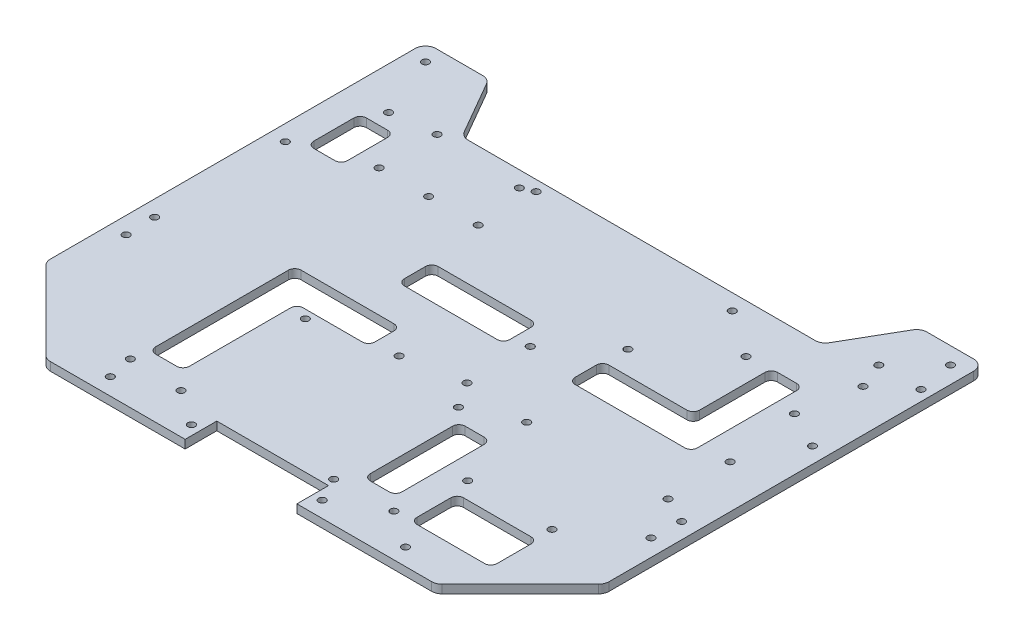
SolidWorks part; units mm, degrees
material "Acier non allié"
ref_plane "Front" through (0, 0, 0) normal (0, 0, 1) x (1, 0, 0)
ref_plane "Top" through (0, 0, 0) normal (0, 1, 0) x (1, 0, 0)
ref_plane "Right" through (0, 0, 0) normal (1, 0, 0) x (0, 0, -1)
sketch "Main scetch" plane through (0, 0, 0) normal (0, 1, 0) x (1, 0, 0)
  line L1 (0, 0) -> (132.5, 0) construction
  line L2 (0, 0) -> (0, 220) construction
  line L3 (0, 220) -> (132.5, 220) construction
  line L4 (132.5, 0) -> (132.5, 220) construction
  line L13 (-92.5, 0) -> (92.5, 0)
  line L14 (92.5, 0) -> (132.5, 40)
  line L15 (132.5, 40) -> (132.5, 220)
  line L16 (132.5, 220) -> (102.5, 220)
  line L17 (102.5, 220) -> (85.1795, 190)
  line L18 (85.1795, 190) -> (-85.1795, 190)
  line L19 (-102.5, 220) -> (-85.1795, 190)
  line L20 (-132.5, 220) -> (-102.5, 220)
  line L21 (-132.5, 40) -> (-132.5, 220)
  line L22 (-92.5, 0) -> (-132.5, 40)
  point P11 (0, 190)
  dimension "132.5" = 132.5
  dimension "D2" = 220
  dimension "D1" = 40
  dimension "D3" = 40
  dimension "D4" = 30
  dimension "D5" = 60
  dimension "D6" = 30
extrude "Main extrusion" add sketch "Main scetch" along normal blind 4
fillet "Congé1" radius 5 10 edges at (-132.5, 2, -40) (-92.5, 2, 0) (92.5, 2, 0) (132.5, 2, -40) (132.5, 2, -220) (102.5, 2, -220) (85.1795, 2, -190) (-85.1795, 2, -190) (-102.5, 2, -220) (-132.5, 2, -220)
sketch "Esquisse1" plane through (0, 4, 0) normal (0, 1, 0) x (1, 0, 0)
  line L0 (0, 0) -> (0, 218.5516) construction
  line L1 (132.5, 42.0711) -> (132.5, 215) construction
  line L2 (127.5, 220) -> (105.3868, 220) construction
  line L3 (-90.4289, 0) -> (90.4289, 0) construction
  circle A0 centre (70, 8) radius 1
  circle A1 centre (124.5, 70) radius 1
  circle A2 centre (124.5, 212) radius 1
  circle A3 centre (-124.5, 212) radius 1
  circle A4 centre (-124.5, 70) radius 1
  circle A5 centre (-70, 8) radius 1
  dimension "D1" = 2
  dimension "D2" = 2
  dimension "D3" = 2
  dimension "D4" = 8
  dimension "D5" = 8
  dimension "D6" = 8
  dimension "D7" = 8
  dimension "D8" = 70
  dimension "D9" = 70
extrude "Enlèv. mat.-Extru.1" cut sketch "Esquisse1" against normal through all
hole_wizard "Dégagement M31" positions "Esquisse2" profile "Esquisse3" hole size "M3" standard "ISO" end condition through all
sketch "Esquisse2" plane through (0, 4, 0) normal (0, 1, 0) x (1, 0, 0)
  point P0 (-124.5, 212)
  point P3 (-124.5, 70)
  point P6 (-70, 8)
  point P9 (70, 8)
  point P12 (124.5, 70)
  point P15 (124.5, 212)
sketch "Esquisse3" plane through (-124.5, 4, -212) normal (1, 0, 0) x (0, 0, 1)
  line L0 (0, 0) -> (0, 4)
  line L1 (0, 4) -> (1.7, 4)
  line L2 (1.7, 4) -> (1.7, 0)
  line L5 (1.7, 0) -> (0, 0)
  line L11 (0, -6.35) -> (0, 107.95) construction
  dimension "Diamètre du perçage jusqu'au prochain" = 3.4
  dimension "Profondeur du perçage jusqu'au prochain" = 4
sketch "Esquisse4" plane through (0, 4, 0) normal (0, 1, 0) x (1, 0, 0)
  line L0 (-132.5, 215) -> (-132.5, 42.0711) construction
  line L1 (-125, 146) -> (-125, 84) construction
  line L2 (82.2927, 190) -> (-82.2927, 190) construction
  line L3 (132.5, 42.0711) -> (132.5, 215) construction
  line L4 (-90.4289, 0) -> (90.4289, 0) construction
  line L5 (127.5, 220) -> (105.3868, 220) construction
  line L8 (-105.3868, 220) -> (-127.5, 220) construction
  line L9 (-31, 7.5) -> (31, 7.5) construction
  line L10 (125, 146) -> (125, 84) construction
  line L11 (-26.5, 0) -> (26.5, 0)
  line L12 (-26.5, 0) -> (-26.5, 15)
  line L13 (-26.5, 15) -> (26.5, 15)
  line L14 (26.5, 0) -> (26.5, 15)
  line L15 (50.5, 182.5) -> (112.5, 182.5) construction
  line L16 (-112.5, 182.5) -> (-50.5, 182.5) construction
  circle A1 centre (-68.5, 185) radius 1 construction
  circle A5 centre (72.5, 167) radius 1
  circle A6 centre (41.5, 142) radius 1
  circle A7 centre (107.5, 155) radius 1
  circle A8 centre (127.5, 195) radius 1
  circle A9 centre (112, 120) radius 1
  circle A10 centre (112.5, 90) radius 1
  circle A11 centre (17.2, 120) radius 1
  circle A12 centre (17.2, 90) radius 1
  circle A13 centre (47.5, 88) radius 1
  circle A14 centre (57.5, 50) radius 1
  circle A15 centre (97.5, 50) radius 1
  circle A16 centre (52.5, 20) radius 1
  circle A17 centre (-10, 85) radius 1
  circle A18 centre (-72.5, 20) radius 1
  circle A19 centre (107.5, 195) radius 1
  circle A23 centre (-47.5, 78) radius 1
  circle A24 centre (25.14, 78) radius 1
  circle A25 centre (-47.5, 19.07) radius 1
  circle A26 centre (25.1096, 18.82) radius 1
  circle A31 centre (-125, 146) radius 1
  circle A32 centre (-125, 84) radius 1
  circle A33 centre (-31, 7.5) radius 1
  circle A34 centre (31, 7.5) radius 1
  circle A35 centre (125, 146) radius 1
  circle A36 centre (125, 84) radius 1
  circle A37 centre (50.5, 182.5) radius 1
  circle A38 centre (112.5, 182.5) radius 1
  circle A39 centre (-112.5, 182.5) radius 1
  circle A40 centre (-50.5, 182.5) radius 1
  circle A41 centre (-45, 185) radius 1
  circle A42 centre (-45, 157.5) radius 1
  circle A43 centre (-68.5, 157.5) radius 1
  circle A44 centre (-92, 157.5) radius 1
  circle A45 centre (-92, 185) radius 1
  point P54 (0, 0)
  point P63 (-125, 115)
  point P69 (0, 7.5)
  point P74 (0, 15)
  point P79 (125, 115)
  dimension "D4" = 2
  dimension "D13" = 2
  dimension "D16" = 2
  dimension "D19" = 2
  dimension "D24" = 2
  dimension "D25" = 2
  dimension "D28" = 2
  dimension "D30" = 2
  dimension "D32" = 2
  dimension "D36" = 2
  dimension "D37" = 2
  dimension "D40" = 2
  dimension "D48" = 2
  dimension "D49" = 2
  dimension "D50" = 2
  dimension "D52" = 2
  dimension "D11" = 2
  dimension "D12" = 2
  dimension "D65" = 2
  dimension "D66" = 2
  dimension "D72" = 2
  dimension "D73" = 2
  dimension "D77" = 2
  dimension "D78" = 2
  dimension "D85" = 2
  dimension "D86" = 2
  dimension "D89" = 2
  dimension "D90" = 2
  dimension "D94" = 2
  dimension "D95" = 2
  dimension "D58" = 2
  dimension "D59" = 2
  dimension "D62" = 2
  dimension "D63" = 2
  dimension "D69" = 2
  dimension "D14" = 205
  dimension "D15" = 23
  dimension "D20" = 25
  dimension "D21" = 65
  dimension "D22" = 5
  dimension "D23" = 25
  dimension "D26" = 20.5
  dimension "D27" = 100
  dimension "D29" = 30
  dimension "D31" = 115.3
  dimension "D33" = 115.3
  dimension "D34" = 132
  dimension "D35" = 85
  dimension "D38" = 50
  dimension "D39" = 75
  dimension "D41" = 35
  dimension "D42" = 80
  dimension "D43" = 20
  dimension "D44" = 20
  dimension "D45" = 205
  dimension "D46" = 85
  dimension "D47" = 142.5
  dimension "D51" = 25
  dimension "D53" = 25
  dimension "D54" = 5
  dimension "D55" = 64
  dimension "D7" = 59.18
  dimension "D8" = 72.64
  dimension "D9" = 58.93
  dimension "D10" = 72.61
  dimension "D67" = 85
  dimension "D68" = 78
  dimension "D17" = 25
  dimension "D18" = 31
  dimension "D76" = 62
  dimension "D74" = 7.5
  dimension "D75" = 105
  dimension "D79" = 7.5
  dimension "D80" = 132.5
  dimension "D81" = 62
  dimension "D82" = 15
  dimension "D83" = 53
  dimension "D84" = 62
  dimension "D87" = 7.5
  dimension "D88" = 105
  dimension "D91" = 62
  dimension "D92" = 7.5
  dimension "D96" = 62
  dimension "D97" = 7.5
  dimension "D98" = 20
  dimension "D93" = 20
  dimension "D56" = 87.5
  dimension "D57" = 5
  dimension "D60" = 27.5
  dimension "D61" = 23.5
  dimension "D64" = 23.5
  dimension "D70" = 27.5
extrude "Enlèv. mat.-Extru.2" cut sketch "Esquisse4" against normal through all
hole_wizard "Dégagement M32" positions "Esquisse5" profile "Esquisse6" hole size "M3" standard "ISO" end condition through all
sketch "Esquisse5" plane through (0, 4, 0) normal (0, 1, 0) x (1, 0, 0)
  point P9 (17.2, 120)
  point P18 (41.5, 142)
  point P21 (72.5, 167)
  point P24 (107.5, 155)
  point P27 (127.5, 195)
  point P30 (112, 120)
  point P33 (112.5, 90)
  point P36 (47.5, 88)
  point P39 (17.2, 90)
  point P42 (57.5, 50)
  point P45 (97.5, 50)
  point P48 (-10, 85)
  point P51 (-72.5, 20)
  point P54 (52.5, 20)
  point P57 (107.5, 195)
  point P86 (-47.5, 78)
  point P89 (25.14, 78)
  point P92 (-47.5, 19.07)
  point P95 (25.1096, 18.82)
  point P114 (-125, 146)
  point P117 (-125, 84)
  point P121 (-31, 7.5)
  point P124 (31, 7.5)
  point P128 (125, 146)
  point P131 (125, 84)
  point P134 (-112.5, 182.5)
  point P137 (-50.5, 182.5)
  point P140 (50.5, 182.5)
  point P143 (112.5, 182.5)
  point P146 (-92, 185)
  point P149 (-92, 157.5)
  point P152 (-68.5, 157.5)
  point P155 (-45, 157.5)
  point P158 (-45, 185)
sketch "Esquisse6" plane through (17.2, 4, -120) normal (1, 0, 0) x (0, 0, 1)
  line L0 (0, 0) -> (0, 4)
  line L1 (0, 4) -> (1.7, 4)
  line L2 (1.7, 4) -> (1.7, 0)
  line L5 (1.7, 0) -> (0, 0)
  line L11 (0, -6.35) -> (0, 107.95) construction
  dimension "Diamètre du perçage jusqu'au prochain" = 3.4
  dimension "Profondeur du perçage jusqu'au prochain" = 4
sketch "Esquisse7" plane through (0, 4, 0) normal (0, 1, 0) x (1, 0, 0)
  line L0 (-90.4289, 0) -> (-26.5, 0) construction
  line L1 (-40.5, 131) -> (9.5, 131)
  line L2 (-40.5, 131) -> (-40.5, 115)
  line L3 (-40.5, 115) -> (9.5, 115)
  line L4 (9.5, 131) -> (9.5, 115)
  line L5 (-132.5, 215) -> (-132.5, 42.0711) construction
  line L8 (40.5, 115) -> (98.5, 115)
  line L10 (132.5, 42.0711) -> (132.5, 215) construction
  line L11 (40.5, 115) -> (40.5, 131)
  line L12 (83.5, 168) -> (98.5, 168)
  line L13 (83.5, 168) -> (83.5, 131)
  line L15 (98.5, 168) -> (98.5, 115)
  line L16 (40.5, 131) -> (83.5, 131)
  line L17 (-105.3868, 220) -> (-127.5, 220) construction
  line L18 (60.5, 42) -> (98.5, 42)
  line L19 (60.5, 42) -> (60.5, 20)
  line L20 (60.5, 20) -> (98.5, 20)
  line L21 (98.5, 42) -> (98.5, 20)
  line L22 (-118.5, 175) -> (-102.5, 175)
  line L23 (-118.5, 175) -> (-118.5, 150)
  line L24 (-118.5, 150) -> (-102.5, 150)
  line L25 (-102.5, 175) -> (-102.5, 150)
  line L27 (-71.5, 28) -> (-55.5, 28)
  line L28 (-71.5, 28) -> (-71.5, 83)
  line L30 (-55.5, 28) -> (-55.5, 82)
  line L31 (31.5, 71.82) -> (46.5, 71.82)
  line L32 (31.5, 71.82) -> (31.5, 26.82)
  line L33 (31.5, 26.82) -> (46.5, 26.82)
  line L34 (46.5, 71.82) -> (46.5, 26.82)
  line L35 (-71.5, 97) -> (-21.5, 97)
  line L36 (-71.5, 97) -> (-71.5, 83)
  line L37 (-55.5, 82) -> (-21.5, 82)
  line L38 (-21.5, 97) -> (-21.5, 82)
  circle A0 centre (-72.5, 20) radius 1.7 construction
  circle A1 centre (-47.5, 78) radius 1.7 construction
  circle A2 centre (25.1096, 18.82) radius 1.7 construction
  circle A3 centre (52.5, 20) radius 1.7 construction
  dimension "D19" = 8
  dimension "D20" = 8
  dimension "D24" = 15
  dimension "D1" = 50
  dimension "D2" = 16
  dimension "D3" = 131
  dimension "D4" = 92
  dimension "D5" = 16
  dimension "D6" = 53
  dimension "D7" = 43
  dimension "D8" = 115
  dimension "D9" = 72
  dimension "D10" = 38
  dimension "D11" = 34
  dimension "D12" = 15
  dimension "D13" = 22
  dimension "D14" = 20
  dimension "D15" = 30
  dimension "D16" = 70
  dimension "D17" = 16
  dimension "D18" = 25
  dimension "D21" = 16
  dimension "D22" = 55
  dimension "D23" = 8
  dimension "6" = 6
  dimension "D25" = 45
  dimension "D26" = 50
  dimension "D27" = 54
  dimension "D28" = 15
extrude "Enlèv. mat.-Extru.3" cut sketch "Esquisse7" against normal up to surface (4 mm away) up to face at (17.2, 0, -118.3)
fillet "Congé2" radius 3 28 edges at (60.5, 2, -42) (60.5, 2, -20) (98.5, 2, -20) (98.5, 2, -42) (98.5, 2, -168) (98.5, 2, -115) (83.5, 2, -168) (40.5, 2, -131) (83.5, 2, -131) (40.5, 2, -115) (-40.5, 2, -115) (9.5, 2, -115) (9.5, 2, -131) (-40.5, 2, -131) (-118.5, 2, -150) (-102.5, 2, -150) (-102.5, 2, -175) (-118.5, 2, -175) (-55.5, 2, -28) (-71.5, 2, -28) (46.5, 2, -26.82) (31.5, 2, -26.82) (46.5, 2, -71.82) (31.5, 2, -71.82) (-21.5, 2, -82) (-21.5, 2, -97) (-55.5, 2, -82) (-71.5, 2, -97)
equation "\"WIDTH\"= 300mm'Total width of the robot"
equation "\"LENGTH\"= 220mm'Total length of the robot"
equation "\"D2@Main scetch\" = \"LENGTH\""
equation "\"CUT_DEPTH\"= 45mm'Depth of the cut on the edges of the plate"
equation "\"Plate_th\"= 3mm'Thickness of the plate"
equation "\"D1\"= \"Plate_th\""
equation "\"D47@Esquisse4\"=(80+205)/2"
